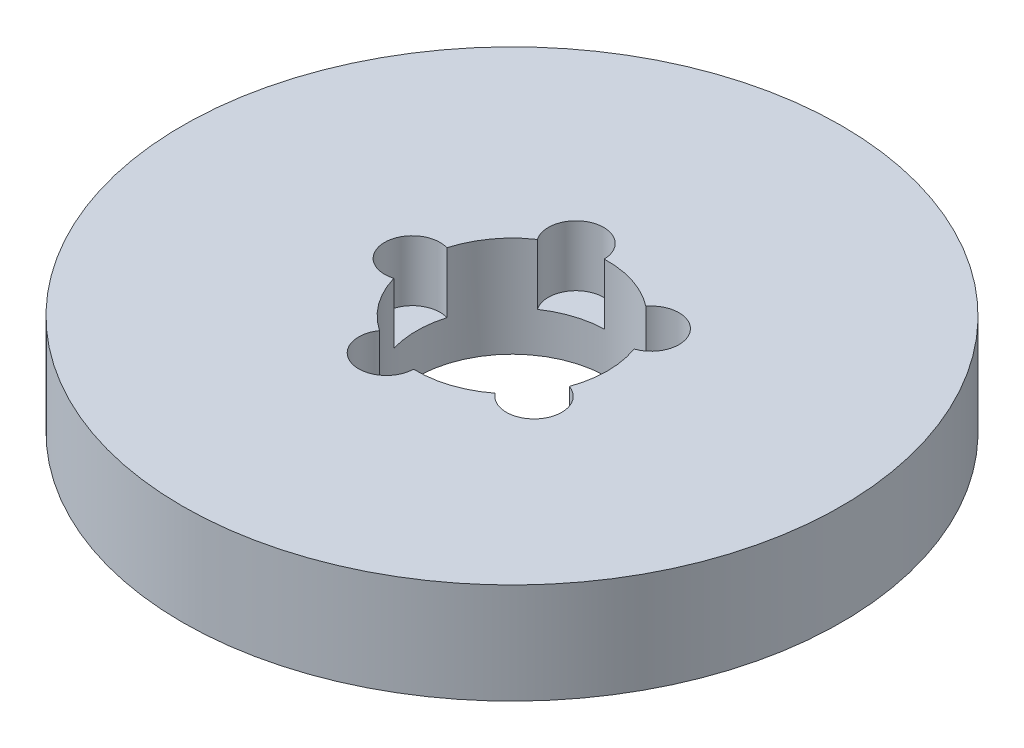
SolidWorks part; units mm, degrees
ref_plane "Front Plane" through (0, 0, 0) normal (0, 0, 1) x (1, 0, 0)
ref_plane "Top Plane" through (0, 0, 0) normal (0, 1, 0) x (1, 0, 0)
ref_plane "Right Plane" through (0, 0, 0) normal (1, 0, 0) x (0, 0, -1)
sketch "Sketch1" plane through (0, 0, 0) normal (0, 1, 0) x (1, 0, 0)
  circle A0 centre (0, 0) radius 95
  dimension "FLANGE_OD" = 190
extrude "Boss-Extrude1" add sketch "Sketch1" along normal blind 29
sketch "Sketch2" plane through (0, 0, 0) normal (0, 1, 0) x (1, 0, 0)
  circle A0 centre (0, 0) radius 27.5
  dimension "BORE_D" = 55
extrude "Cut-Extrude1" cut sketch "Sketch2" along normal through all
sketch "Sketch3" plane through (0, 29, 0) normal (0, 1, 0) x (1, 0, 0)
  circle A0 centre (0, 0) radius 28.7401 construction
  circle A1 centre (-28.7401, 0) radius 7.9902
  dimension "BOLT_D" = 15.9805
  dimension "BOLT_PCD" = 57.4802
extrude "Cut-Extrude2" cut sketch "Sketch3" against normal blind 17.4577
pattern_circular "CirPattern1" count 5 over 360 about axis through (0, 0, 0) along (0, 1, 0) of "Cut-Extrude2"
